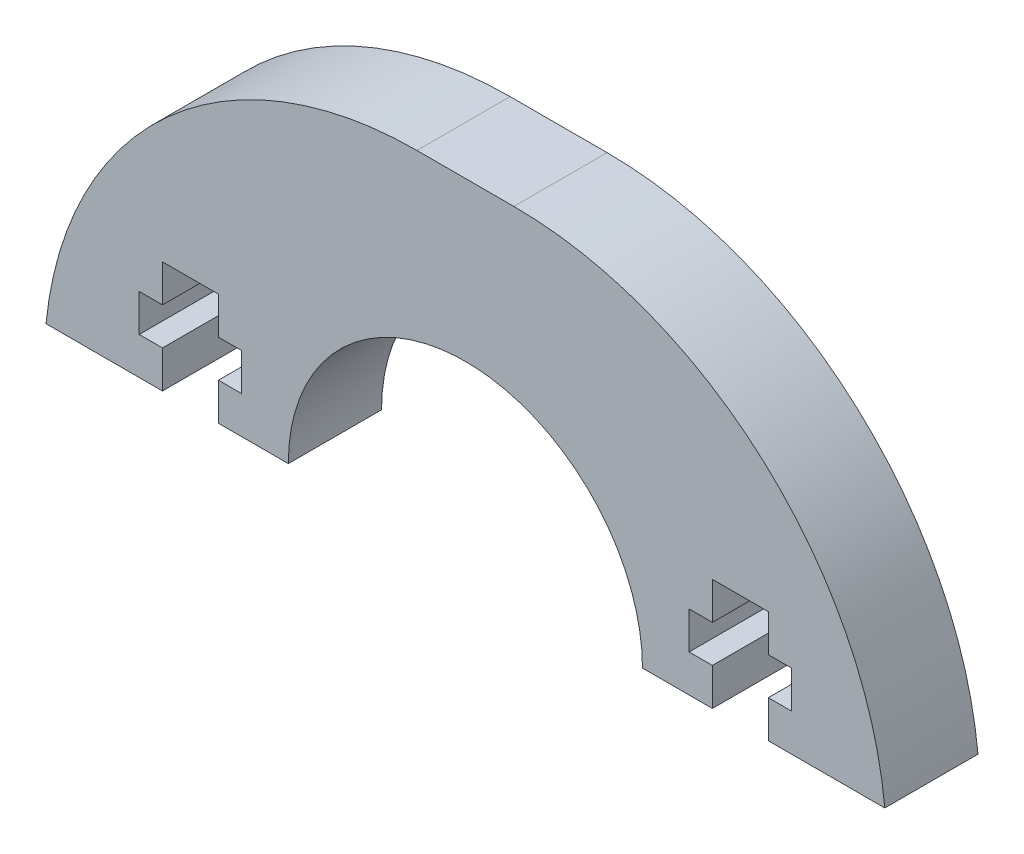
SolidWorks part; units mm, degrees
ref_plane "Front Plane" through (0, 0, 0) normal (0, 0, 1) x (1, 0, 0)
ref_plane "Top Plane" through (0, 0, 0) normal (0, 1, 0) x (1, 0, 0)
ref_plane "Right Plane" through (0, 0, 0) normal (1, 0, 0) x (0, 0, -1)
sketch "Sketch1" plane through (0, 0, 0) normal (0, 0, 1) x (1, 0, 0)
  line L0 (16.25, -3) -> (13.25, -3)
  line L1 (22.5, 9) -> (-22.5, 9)
  line L2 (22.5, 9) -> (22.5, -9)
  line L3 (22.5, -9) -> (-22.5, -9)
  line L4 (-22.5, 9) -> (-22.5, -9)
  line L5 (22.5, 9) -> (-22.5, -9) construction
  line L6 (22.5, -9) -> (-22.5, 9) construction
  line L7 (-13.25, -3) -> (-16.25, -3)
  line L8 (-13.25, -3) -> (-13.25, -9)
  line L9 (-13.25, -9) -> (-16.25, -9)
  line L10 (-16.25, -3) -> (-16.25, -9)
  line L11 (-13.25, -3) -> (-16.25, -9) construction
  line L12 (-13.25, -9) -> (-16.25, -3) construction
  line L13 (-17.5, -5) -> (-12, -5)
  line L14 (-17.5, -5) -> (-17.5, -7)
  line L15 (-17.5, -7) -> (-12, -7)
  line L16 (-12, -5) -> (-12, -7)
  line L17 (-17.5, -5) -> (-12, -7) construction
  line L18 (-17.5, -7) -> (-12, -5) construction
  line L19 (16.25, -3) -> (16.25, -9)
  line L20 (16.25, -9) -> (13.25, -9)
  line L21 (13.25, -3) -> (13.25, -9)
  line L22 (12, -5) -> (17.5, -5)
  line L23 (12, -5) -> (12, -7)
  line L24 (12, -7) -> (17.5, -7)
  line L25 (17.5, -5) -> (17.5, -7)
  line L26 (16.25, -3) -> (13.25, -9) construction
  line L27 (16.25, -9) -> (13.25, -3) construction
  line L28 (12, -5) -> (17.5, -7) construction
  line L29 (12, -7) -> (17.5, -5) construction
  line L30 (-12, -7) -> (12, -7) construction
  line L31 (0, 0) -> (0, -7) construction
  circle A0 centre (0, -9) radius 9.5
  point P0 (0, 0)
  point P6 (-14.75, -6)
  point P11 (-14.75, -6)
  point P18 (14.75, -6)
  point P23 (14.75, -6)
  dimension "D9" = 19
  dimension "D1" = 2
  dimension "D2" = 5.5
  dimension "D3" = 3
  dimension "D4" = 6
  dimension "D6" = 18
  dimension "D7" = 45
  dimension "D8" = 5
  dimension "D5" = 2
extrude "Boss-Extrude1" add sketch "Sketch1" along normal blind 5 contours A0 L3 L21 L24 L23 L22 L0 L19 L25 L2 L1 L4 L10 L15 L14 L13 L7 L8 L16 region at (0, 1.5754, 0)
fillet "Fillet1" radius 20 2 edges at (22.5, 9, 2.5) (-22.5, 9, 2.5)
